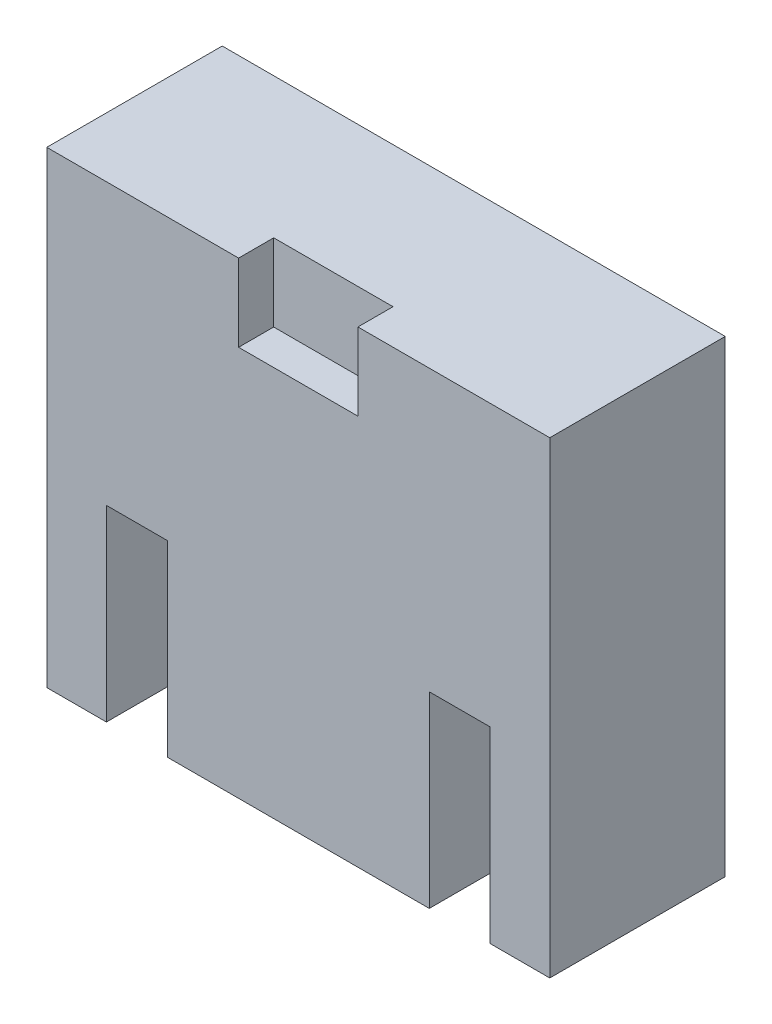
SolidWorks part; units mm, degrees
ref_plane "Front Plane" through (0, 0, 0) normal (0, 0, 1) x (1, 0, 0)
ref_plane "Top Plane" through (0, 0, 0) normal (0, 1, 0) x (1, 0, 0)
ref_plane "Right Plane" through (0, 0, 0) normal (1, 0, 0) x (0, 0, -1)
sketch "Sketch1" plane through (0, 0, 0) normal (0, 0, 1) x (1, 0, 0)
  line L1 (-19.7512, 21.2775) -> (23.2488, 21.2775)
  line L2 (-19.7512, 21.2775) -> (-19.7512, -18.7225)
  line L3 (-19.7512, -18.7225) -> (23.2488, -18.7225)
  line L4 (23.2488, 21.2775) -> (23.2488, -18.7225)
  dimension "D1" = 43
  dimension "D2" = 40
extrude "Boss-Extrude1" add sketch "Sketch1" along normal blind 15
sketch "Sketch3" plane through (0, 0, 15) normal (0, 0, 1) x (1, 0, 0)
  line L0 (-19.7512, -18.7225) -> (23.2488, -18.7225) construction
  line L1 (-14.6512, -18.7225) -> (-9.4512, -18.7225)
  line L2 (-14.6512, -18.7225) -> (-14.6512, -2.6815)
  line L3 (-14.6512, -2.6815) -> (-9.4512, -2.6815)
  line L4 (-9.4512, -18.7225) -> (-9.4512, -2.6815)
  line L5 (1.7488, 21.2775) -> (1.7488, -18.7225)
  line L6 (23.2488, 21.2775) -> (-19.7512, 21.2775) construction
  line L7 (18.1488, -2.6815) -> (12.9488, -2.6815)
  line L8 (12.9488, -18.7225) -> (12.9488, -2.6815)
  line L9 (18.1488, -18.7225) -> (12.9488, -18.7225)
  line L10 (18.1488, -18.7225) -> (18.1488, -2.6815)
  line L12 (-3.3512, 21.2775) -> (6.8488, 21.2775)
  line L13 (-3.3512, 21.2775) -> (-3.3512, 14.6722)
  line L14 (-3.3512, 14.6722) -> (6.8488, 14.6722)
  line L15 (6.8488, 21.2775) -> (6.8488, 14.6722)
  point P6 (1.7488, -18.7225)
  point P19 (1.7488, 21.2775)
  line M8 (-19.7512, -18.7225) -> (23.2488, -18.7225)
  line M10 (23.2488, 21.2775) -> (-19.7512, 21.2775)
  dimension "D1" = 5.2
  dimension "D2" = 16.4
  dimension "D3" = 0
  dimension "D4" = 10.2
extrude "Cut-Extrude1" cut sketch "Sketch3" against normal blind 3 contours L13 L14 L5 M10 | L15 L5 L14 M10 region at (4.2988, 17.9748, 15) region at (-0.8012, 17.9748, 15)
extrude "Cut-Extrude2" cut sketch "Sketch3<4>" against normal blind 10 contours L4 L3 L2 M8 | L10 L7 L8 M8 region at (-12.0512, -10.702, 15) region at (15.5488, -10.702, 15)
sketch "Sketch3<4>" plane through (0, 0, 15) normal (0, 0, 1) x (1, 0, 0) same geometry as "Sketch3"
